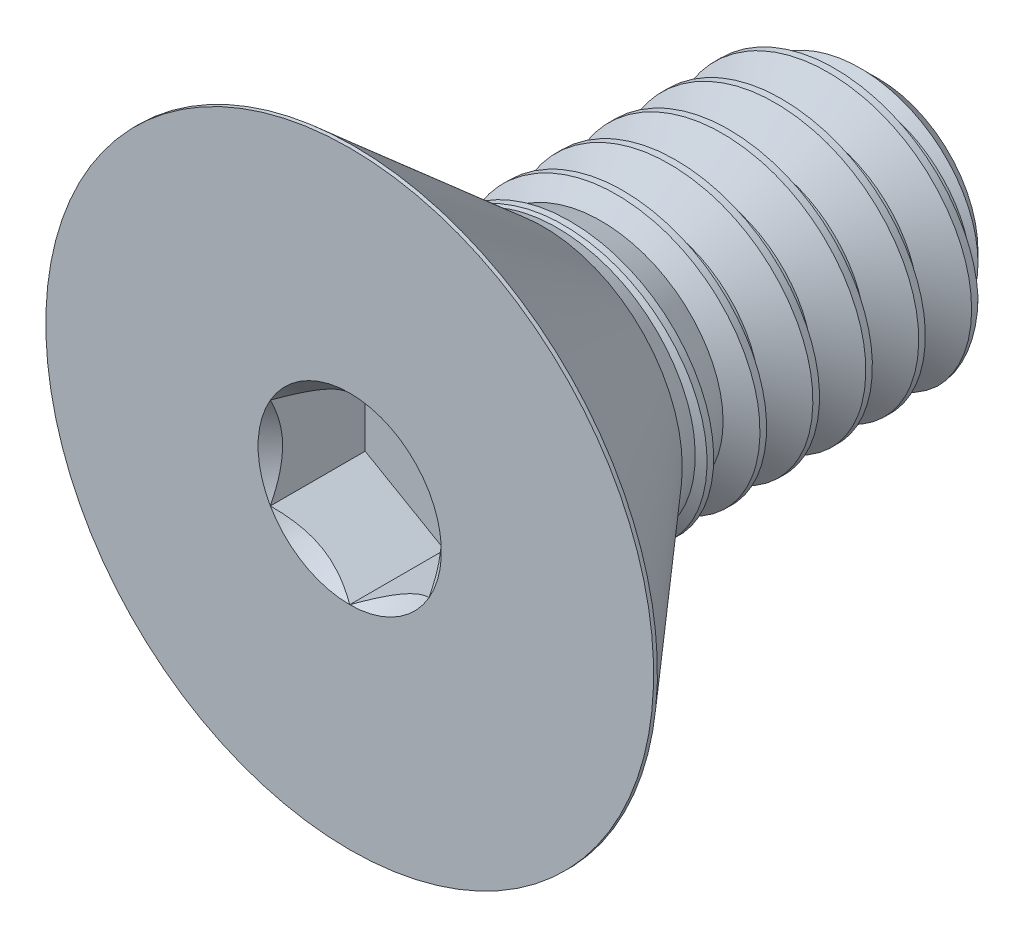
SolidWorks part; units mm, degrees
ref_plane "Front Plane" through (0, 0, 0) normal (0, 0, 1) x (1, 0, 0)
ref_plane "Top Plane" through (0, 0, 0) normal (0, 1, 0) x (1, 0, 0)
ref_plane "Right Plane" through (0, 0, 0) normal (1, 0, 0) x (0, 0, -1)
sketch "Sketch1" plane through (0, 0, 0) normal (1, 0, 0) x (0, 0, -1)
  line L0 (-3.9688, 0) -> (3.9688, 0) construction
  line L1 (-3.9688, 0) -> (-3.9688, 4.5593)
  line L2 (-3.9688, 4.5593) -> (-3.9119, 4.5593)
  line L3 (-3.9119, 4.5593) -> (-1.1239, 2.1358)
  line L4 (-3.9119, -4.5593) -> (-1.1239, -2.1358)
  line L5 (3.9688, 0) -> (3.9687, 2.0828)
  line L6 (3.9687, 2.0828) -> (-1.1239, 2.0828)
  line L7 (3.3734, 2.0828) -> (3.9688, 1.4875)
  line L8 (3.9191, 2.1687) -> (4.316, 1.4813) construction
  line L9 (4.316, 1.4813) -> (4.7129, 2.1687) construction
  line L10 (4.7129, 2.1687) -> (3.9191, 2.1687) construction
  line L11 (3.9439, 2.1258) -> (4.6881, 2.1258)
  line L12 (4.6881, 2.1258) -> (4.3656, 1.5672)
  line L13 (4.3656, 1.5672) -> (4.2664, 1.5672)
  line L14 (4.2664, 1.5672) -> (3.9439, 2.1258)
  line L15 (4.316, 1.5672) -> (4.316, 1.4813) construction
  line L16 (3.9687, 2.0828) -> (4.6633, 2.0828) construction
  line L17 (4.316, 2.1687) -> (4.316, 2.0828) construction
  line L18 (3.9688, -2.0828) -> (-1.1239, -2.0828)
  arc A0 (-1.1239, 2.1358) -> (-0.9822, 2.0828) centre (-0.9822, 2.2989) ccw
  point P2 (0, 0)
  point P23 (-2.5464, 0)
  point P27 (4.316, 2.1258)
  point P30 (2.7781, -2.0828)
  point P31 (-1.1239, 4.5593)
  point P33 (-1.1239, -4.5593)
  point P34 (-3.9119, -4.5593)
  point P35 (-3.9688, 4.5593)
  dimension "Length" = 7.9375
  dimension "Head Height" = 2.8448
  dimension "Head Diameter" = 9.1186
  dimension "Countersink Angle" = 82
  dimension "Screw Size Decimal Equivalent" = 4.1656
  dimension "Pitch" = 0.7937
  dimension "D4" = 0.0992
  dimension "D3" = 45
  dimension "D5" = 0.5953
  dimension "D6" = 1.4224
  dimension "D1" = 1.1906
  dimension "D7" = 0.0569
sketch "Sketch8" plane through (0, 0, 0) normal (0, 0, 1) x (1, 0, 0)
  line L1 (0, 1.3748) -> (-1.1906, 0.6874)
  line L2 (-1.1906, 0.6874) -> (-1.1906, -0.6874)
  line L3 (-1.1906, -0.6874) -> (0, -1.3748)
  line L4 (0, -1.3748) -> (1.1906, -0.6874)
  line L5 (1.1906, -0.6874) -> (1.1906, 0.6874)
  line L6 (1.1906, 0.6874) -> (0, 1.3748)
  circle A0 centre (0, 0) radius 1.1906 construction
  dimension "Drive Size" = 2.3813
sketch "Sketch2" plane through (0, 0, 0) normal (1, 0, 0) x (0, 0, -1)
  line L0 (-3.9119, 4.5593) -> (-1.1239, 2.1358) construction
  line L1 (-3.9688, 0) -> (-3.9688, 4.5593) construction
  line L2 (-3.9119, 4.5593) -> (-1.063, 2.0828)
  line L3 (-3.9688, 0) -> (-3.9688, 4.5593)
  line L4 (-3.9688, 4.5593) -> (-3.9119, 4.5593) construction
  line L5 (-3.9688, 4.5593) -> (-3.9119, 4.5593)
  line L6 (-1.063, 2.0828) -> (3.3734, 2.0828)
  line L7 (3.3734, 2.0828) -> (3.9688, 1.4875)
  line L8 (3.9688, 1.4875) -> (3.9688, 0)
  line L9 (3.9688, 0) -> (-3.9688, 0)
revolve "Revolve1" add sketch "Sketch2" angle 360 about L9
sketch "Sketch9" plane through (0, 0, 3.9688) normal (0, 0, 1) x (1, 0, 0)
  line L0 (1.1906, -0.6874) -> (1.1906, 0.6874) construction
  line L1 (0, -1.3748) -> (1.1906, -0.6874) construction
  line L2 (-1.1906, -0.6874) -> (0, -1.3748) construction
  line L3 (-1.1906, 0.6874) -> (-1.1906, -0.6874) construction
  line L4 (0, 1.3748) -> (-1.1906, 0.6874) construction
  line L5 (1.1906, 0.6874) -> (0, 1.3748) construction
  line L6 (1.1906, -0.6874) -> (1.1906, 0.6874)
  line L7 (0, -1.3748) -> (1.1906, -0.6874)
  line L8 (-1.1906, -0.6874) -> (0, -1.3748)
  line L9 (-1.1906, 0.6874) -> (-1.1906, -0.6874)
  line L10 (0, 1.3748) -> (-1.1906, 0.6874)
  line L11 (1.1906, 0.6874) -> (0, 1.3748)
sketch "Sketch10" plane through (0, 0, 3.9688) normal (0, 0, 1) x (1, 0, 0)
  circle A0 centre (0, 0) radius 1.3748
extrude "Cut-Extrude2" cut sketch "Sketch10" against normal up to vertex (1.4224 mm away) draft 45 up to point (0, 0, 2.5464)
extrude "Cut-Extrude1" cut sketch "Sketch9" against normal up to vertex (1.4224 mm away) up to point (0, 0, 2.5464)
ref_plane "Plane1" through (0, 0, 1.063) normal (0, 0, 1) x (1, 0, 0)
split "Split1" trim tools "Plane1" bodies to split 111 resulting bodies 105 106
sketch "Sketch3" plane through (0, 0, -3.9688) normal (0, 0, -1) x (-1, 0, 0)
  circle A0 centre (0, 0) radius 2.0828 construction
  circle A1 centre (0, 0) radius 2.0828
curve "Helix/Spiral1" pitch 0.7937 height 7.9375 radius 2.0828 centre (0, 0, -3.9688) axis (0, 0, 1) start towards (0, 1, 0)
sketch "Sketch4" plane through (0, 0, 0) normal (1, 0, 0) x (0, 0, -1)
  line L0 (3.9439, 2.1258) -> (4.6881, 2.1258) construction
  line L1 (4.2664, 1.5672) -> (3.9439, 2.1258) construction
  line L2 (4.3656, 1.5672) -> (4.2664, 1.5672) construction
  line L3 (4.6881, 2.1258) -> (4.3656, 1.5672) construction
  line L4 (3.9439, 2.1258) -> (4.6881, 2.1258)
  line L5 (4.2664, 1.5672) -> (3.9439, 2.1258)
  line L6 (4.3656, 1.5672) -> (4.2664, 1.5672)
  line L7 (4.6881, 2.1258) -> (4.3656, 1.5672)
sweep "Cut-Sweep1" cut profiles "Sketch4" path "Helix/Spiral1" align with end faces yes
sketch "Sketch7" plane through (0, 0, 1.063) normal (0, 0, 1) x (1, 0, 0)
  circle A0 centre (0, 0) radius 2.0828
extrude "Boss-Extrude2" add sketch "Sketch7" against normal up to next (5.0317 mm away) draft 20
equation "\"D4@Sketch1\" = \"Pitch@Sketch1\" / 8"
equation "\"D5@Sketch1\"=\"Pitch@Sketch1\"*0.75"
equation "\"D4@Helix/Spiral1\"=\"Pitch@Sketch1\""
equation "\"D3@Helix/Spiral1\"=\"Length@Sketch1\""
equation "\"D6@Sketch1\"=\"Head Height@Sketch1\"/2"
equation "\"D1@Sketch1\"=\"Pitch@Sketch1\"*1.5"
equation "\"D7@Sketch1\"=\"Head Height@Sketch1\"*0.02"
